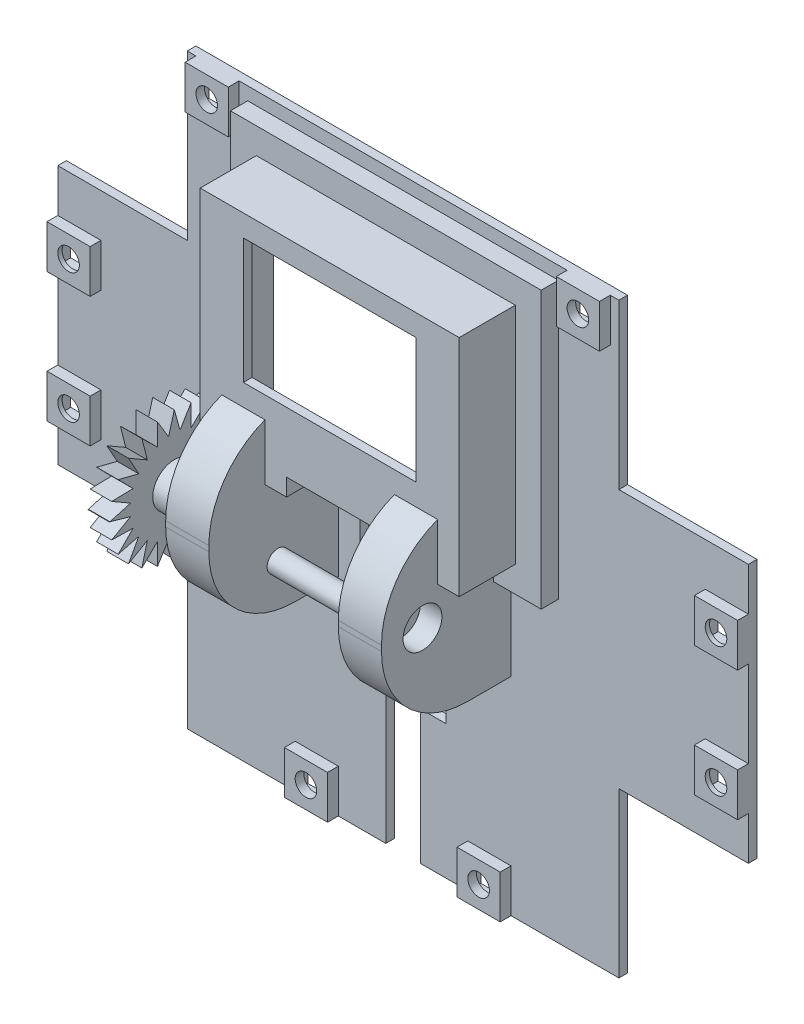
SolidWorks part; units mm, degrees
material "ABS"
ref_plane "Plan de face" through (0, 0, 0) normal (0, 0, 1) x (1, 0, 0)
ref_plane "Plan de dessus" through (0, 0, 0) normal (0, 1, 0) x (1, 0, 0)
ref_plane "Plan de droite" through (0, 0, 0) normal (1, 0, 0) x (0, 0, -1)
sketch "Esquisse1" plane through (0, 0, 0) normal (0, 0, 1) x (1, 0, 0)
  line L0 (0, 0) -> (0, 87) construction
  line L1 (-50, -68) -> (50, -68)
  line L2 (-50, -68) -> (-50, 68)
  line L3 (-50, 68) -> (50, 68)
  line L4 (50, -68) -> (50, 68)
  line L5 (-50, -68) -> (50, 68) construction
  line L6 (-50, 68) -> (50, -68) construction
  line L7 (-34, 3) -> (34, 3)
  line L8 (-34, 3) -> (-34, 63)
  line L9 (-34, 63) -> (34, 63)
  line L10 (34, 3) -> (34, 63)
  line L11 (0, 87) -> (0, -87) construction
  line L13 (-10, 3) -> (10, 3)
  line L14 (-10, 3) -> (-10, -37)
  line L15 (-10, -68) -> (10, -68)
  line L16 (10, 3) -> (10, -37)
  line L17 (-10, 3) -> (10, 3)
  line L18 (-10, 3) -> (-10, -37)
  line L19 (-10, -37) -> (10, -37)
  line L20 (10, 3) -> (10, -37)
  point P0 (0, 0)
  dimension "D1" = 136
  dimension "D2" = 100
  dimension "D3" = 68
  dimension "D4" = 60
  dimension "D5" = 16
  dimension "D6" = 5
  dimension "D7" = 174
  dimension "D8" = 87
  dimension "D9" = 20
  dimension "D10" = 24
  dimension "D11" = 40
extrude "Boss.-Extru.1" add sketch "Esquisse1" along normal blind 2 contours L1 L4 L3 L2 L19 L14 L7 L8 L9 L10 L16 region at (-48.3119, 0, 0)
sketch "Esquisse2" plane through (0, 0, 2) normal (0, 0, 1) x (1, 0, 0)
  line L0 (-34, 63) -> (34, 63) construction
  line L1 (-36, 65) -> (36, 65)
  line L2 (-36, 65) -> (-36, 1)
  line L3 (-36, 1) -> (36, 1)
  line L4 (36, 65) -> (36, 1)
  line L5 (-34, 3) -> (-34, 63) construction
  line L6 (34, 3) -> (34, 63) construction
  line L7 (10, 3) -> (34, 3) construction
  line L9 (-34, 63) -> (34, 63)
  line L10 (-34, 63) -> (-34, 3)
  line L11 (-34, 3) -> (34, 3)
  line L12 (34, 63) -> (34, 3)
  line L13 (-10, 3) -> (10, 3)
  line L14 (-10, 3) -> (-10, 1)
  line L15 (-10, 1) -> (10, 1)
  line L16 (10, 3) -> (10, 1)
  line M6 (-10, -37) -> (-10, 3)
  line M7 (-10, 3) -> (-34, 3)
  line M8 (-34, 3) -> (-34, 63)
  line M9 (-34, 63) -> (34, 63)
  line M10 (34, 63) -> (34, 3)
  line M11 (34, 3) -> (10, 3)
  line M12 (10, 3) -> (10, -37)
  dimension "D1" = 2
  dimension "D2" = 2
  dimension "D3" = 2
  dimension "D4" = 2
  dimension "D5" = 20
extrude "Boss.-Extru.2" add sketch "Esquisse2" along normal blind 4 contours L4 L1 L2 L3 M6 M7 M8 M9 M10 M11 M12 region at (0, 64.0367, 2)
sketch "Esquisse3" plane through (0, 0, 6) normal (0, 0, 1) x (1, 0, 0)
  line L1 (-34, 63) -> (34, 63)
  line L2 (-34, 63) -> (-34, 3)
  line L3 (-34, 3) -> (34, 3)
  line L4 (34, 63) -> (34, 3)
  line L5 (-28, 57) -> (28, 57)
  line L6 (-28, 57) -> (-28, 9)
  line L7 (-28, 9) -> (28, 9)
  line L8 (28, 57) -> (28, 9)
  dimension "D1" = 6
  dimension "D2" = 6
  dimension "D3" = 6
  dimension "D4" = 6
extrude "Boss.-Extru.3" add sketch "Esquisse3" against normal blind 2
sketch "Esquisse4" plane through (0, 0, 6) normal (0, 0, 1) x (1, 0, 0)
  line L1 (-28, 57) -> (28, 57)
  line L2 (-28, 57) -> (-28, 9)
  line L3 (-28, 9) -> (28, 9)
  line L4 (28, 57) -> (28, 9)
  line L5 (-30, 59) -> (30, 59)
  line L6 (-30, 59) -> (-30, 7)
  line L7 (-30, 7) -> (30, 7)
  line L8 (30, 59) -> (30, 7)
  dimension "D1" = 2
  dimension "D2" = 2
  dimension "D3" = 2
  dimension "D4" = 2
extrude "Boss.-Extru.4" add sketch "Esquisse4" along normal blind 13
sketch "Esquisse5" plane through (0, 0, 19) normal (0, 0, 1) x (1, 0, 0)
  line L1 (-28, 57) -> (28, 57)
  line L2 (-28, 57) -> (-28, 9)
  line L3 (-28, 9) -> (28, 9)
  line L4 (28, 57) -> (28, 9)
extrude "Boss.-Extru.5" add sketch "Esquisse5" against normal blind 2
sketch "Esquisse6" plane through (0, 0, 19) normal (0, 0, 1) x (1, 0, 0)
  line L1 (-10, 1) -> (10, 1)
  line L2 (-10, 1) -> (-10, 11)
  line L3 (-10, 11) -> (10, 11)
  line L4 (10, 1) -> (10, 11)
  dimension "D1" = 20
  dimension "D2" = 10
extrude "Enlèv. mat.-Extru.1" cut sketch "Esquisse6" against normal blind 35
sketch "Esquisse9" plane through (0, 0, 2) normal (0, 0, 1) x (1, 0, 0)
  line L0 (0, 0) -> (50, 0) construction
  line L1 (50, -68) -> (50, 68) construction
  line L2 (50, 0) -> (-50, 0) construction
  line L3 (-50, -68) -> (-50, 68) construction
  line L4 (-36, 1) -> (-10, 1) construction
  line L5 (-50, 20) -> (-48, 20)
  line L6 (-50, 20) -> (-50, -20)
  line L7 (-50, -20) -> (-48, -20)
  line L8 (-48, 20) -> (-48, -20)
  line L9 (50, 20) -> (48, 20)
  line L10 (50, 20) -> (50, -20)
  line L11 (50, -20) -> (48, -20)
  line L12 (48, 20) -> (48, -20)
  line L13 (-25, -20) -> (-15, -20)
  line L14 (-25, -20) -> (-25, 1)
  line L15 (-25, 1) -> (-15, 1)
  line L16 (-15, -20) -> (-15, 1)
  line L17 (10, 1) -> (36, 1) construction
  line L18 (15, 1) -> (25, 1)
  line L19 (15, 1) -> (15, -20)
  line L20 (15, -20) -> (25, -20)
  line L21 (25, 1) -> (25, -20)
  line L22 (-10, 1) -> (-10, -37) construction
  line L23 (10, 1) -> (10, -37) construction
  dimension "D1" = 2
  dimension "D2" = 40
  dimension "D3" = 20
  dimension "D4" = 40
  dimension "D5" = 2
  dimension "D6" = 20
  dimension "D7" = 10
  dimension "D8" = 10
  dimension "D9" = 21
  dimension "D10" = 21
  dimension "D11" = 5
  dimension "D12" = 5
extrude "Boss.-Extru.9" add sketch "Esquisse9" along normal blind 30
fillet "Congé5" radius 20 4 edges at (49, -20, 32) (49, 20, 32) (-49, -20, 32) (-49, 20, 32)
sketch "Esquisse10" plane through (0, 0, 6) normal (0, 0, 1) x (1, 0, 0)
  line L0 (-30, 7) -> (-10, 7) construction
  line L1 (-25, 1) -> (-15, 1)
  line L2 (-25, 1) -> (-25, 7)
  line L3 (-25, 7) -> (-15, 7)
  line L4 (-15, 1) -> (-15, 7)
  line L5 (10, 7) -> (30, 7) construction
  line L6 (15, 1) -> (25, 1)
  line L7 (15, 1) -> (15, 7)
  line L8 (15, 7) -> (25, 7)
  line L9 (25, 1) -> (25, 7)
  dimension "D1" = 10
  dimension "D2" = 10
extrude "Boss.-Extru.10" add sketch "Esquisse10" along normal blind 26
sketch "Esquisse11" plane through (0, 0, 19) normal (0, 0, 1) x (1, 0, 0)
  line L1 (-25, 7) -> (-15, 7)
  line L2 (-25, 7) -> (-25, 20)
  line L3 (-25, 20) -> (-15, 20)
  line L4 (-15, 7) -> (-15, 20)
  line L5 (15, 7) -> (25, 7)
  line L6 (15, 7) -> (15, 20)
  line L7 (15, 20) -> (25, 20)
  line L8 (25, 7) -> (25, 20)
  dimension "D1" = 13
  dimension "D2" = 13
  dimension "D3" = 10
  dimension "D4" = 10
extrude "Boss.-Extru.11" add sketch "Esquisse11" along normal blind 13
fillet "Congé6" radius 20 2 edges at (20, 20, 32) (-20, 20, 32)
fillet "Congé7" radius 20 2 edges at (20, -20, 32) (-20, -20, 32)
sketch "Esquisse12" plane through (-15, 0, 0) normal (1, 0, 0) x (0, 0, -1)
  line L0 (0, 0) -> (-32, 0) construction
  line L1 (-16, 0) -> (-16, -19.5959) construction
  line L2 (-16, 0) -> (-16, -9.798) construction
  arc A0 (-32, 0) -> (-12, -20) centre (-12, 0) ccw construction
  circle A1 centre (-16, -9.798) radius 2.5
  dimension "D1" = 5
extrude "Boss.-Extru.12" add sketch "Esquisse12" along normal blind 36
sketch "Esquisse13" plane through (50, 0, 0) normal (1, 0, 0) x (0, 0, -1)
  line L0 (0, 0) -> (-32, 0) construction
  line L1 (-32, 0) -> (-27, 0) construction
  arc A0 (-32, 0) -> (-12, -20) centre (-12, 0) ccw construction
  circle A1 centre (-22.5, 0) radius 4.5
  dimension "D2" = 9
  dimension "D1" = 5
extrude "Enlèv. mat.-Extru.2" cut sketch "Esquisse13" against normal blind 30
sketch "Esquisse14" plane through (-50, 0, 0) normal (-1, 0, 0) x (0, 0, 1)
  line L0 (0, 0) -> (32, 0) construction
  line L1 (32, 0) -> (27, 0) construction
  circle A0 centre (22.5, 0) radius 4.5
  dimension "D2" = 9
  dimension "D1" = 5
extrude "Enlèv. mat.-Extru.4" cut sketch "Esquisse14" against normal blind 17
sketch "Esquisse15" plane through (-25, 0, 0) normal (-1, 0, 0) x (0, 0, 1)
  line L0 (0, 0) -> (32, 0) construction
  line L1 (32, 0) -> (27.5, 0) construction
  circle A0 centre (22.5, 0) radius 5
  dimension "D2" = 10
  dimension "D1" = 4.5
extrude "Boss.-Extru.13" add sketch "Esquisse15" along normal blind 12.5
sketch "Esquisse16" plane through (0, 0, 2) normal (0, 0, 1) x (1, 0, 0)
  line L0 (-47.5, 0) -> (47.5, 0) construction
  line L1 (-47.5, 0) -> (-38, 0) construction
  line L2 (-38, 0) -> (-37.5, 0) construction
  line L4 (-37.5, 0) -> (-36.5, 0)
  line L5 (-37.5, 0) -> (-37.5, 1)
  line L6 (-37.5, 1) -> (-36.5, 1)
  line L7 (-36.5, 0) -> (-36.5, 1)
  line L8 (-37.5, 0) -> (-36.5, 0)
  line L9 (-37.5, 0) -> (-37.5, -1)
  line L10 (-37.5, -1) -> (-36.5, -1)
  line L11 (-36.5, 0) -> (-36.5, -1)
  dimension "D1" = 95
  dimension "D2" = 2.5
  dimension "D3" = 9.5
  dimension "D4" = 0.5
  dimension "D5" = 1
  dimension "D6" = 1
  dimension "D7" = 1
extrude "Boss.-Extru.14" add sketch "Esquisse16" along normal blind 2 contours L4 L7 L6 L5 | L11 L4 L9 L10 region at (-37, 0.5, 2) region at (-37, -0.5, 2)
sketch "Esquisse17" plane through (-37.5, 0, 0) normal (-1, 0, 0) x (0, 0, 1)
  line L0 (22.5, 5) -> (22.5, -5) construction
  line L1 (0, 0) -> (22.5, 0) construction
  circle A0 centre (22.5, 0) radius 5 construction
  circle A1 centre (22.5, 0) radius 5 construction
  circle A2 centre (22.5, 0) radius 15
  dimension "D1" = 30
extrude "Boss.-Extru.16" add sketch "Esquisse17" against normal blind 5
sketch "Esquisse18" plane through (-50, 0, 0) normal (-1, 0, 0) x (0, 0, 1)
  circle A0 centre (22.5, 0) radius 4.5
extrude "Enlèv. mat.-Extru.5" cut sketch "Esquisse18" against normal blind 16
sketch "Esquisse23" plane through (-37.5, 0, 0) normal (-1, 0, 0) x (0, 0, 1)
  line L0 (22.5, 0) -> (22.5, 15) construction
  line L1 (22.5, 15) -> (22.5, -15) construction
  line L2 (22.5, 0) -> (7.5, 0) construction
  line L3 (7.5, 0) -> (37.5, 0) construction
  line L4 (22.5, 15) -> (23.92, 9.8987)
  line L5 (22.5, 15) -> (21.07, 9.8972)
  line L6 (21.3706, 9.936) -> (18.6136, 14.4878)
  line L7 (18.6136, 14.4878) -> (18.6136, 9.2139)
  line L8 (22.5, 0) -> (18.6136, 14.4878) construction
  line L9 (22.5, 0) -> (14.9926, 12.9861) construction
  line L10 (22.5, 0) -> (11.8844, 10.5976) construction
  line L11 (22.5, 0) -> (9.5011, 7.4853) construction
  line L12 (22.5, 0) -> (8.0056, 3.8618) construction
  line L13 (11.8844, 10.5976) -> (16.4547, 7.9658)
  line L14 (14.4531, 5.937) -> (11.8844, 10.5976)
  line L15 (9.5011, 7.4853) -> (13.2133, 3.7091)
  line L16 (9.5011, 7.4853) -> (14.6367, 6.1781)
  line L17 (14.9926, 12.9861) -> (18.7752, 9.2804)
  line L18 (14.9926, 12.9861) -> (16.3085, 7.8527)
  line L19 (13.3259, 3.9795) -> (8.0056, 3.8618)
  line L20 (8.0056, 3.8618) -> (12.5759, 1.23)
  line L21 (7.5, -0.0255) -> (12.6004, 1.4132)
  line L22 (7.5, -0.0255) -> (12.6038, -1.4368)
  line L23 (37.5, -0.0255) -> (32.3996, 1.4132)
  line L24 (35.4989, 7.4853) -> (31.7867, 3.7091)
  line L25 (36.9944, 3.8618) -> (32.4241, 1.23)
  line L26 (31.6741, 3.9795) -> (36.9944, 3.8618)
  line L27 (35.4989, 7.4853) -> (30.3633, 6.1781)
  line L28 (30.5469, 5.937) -> (33.1156, 10.5976)
  line L29 (33.1156, 10.5976) -> (28.5453, 7.9658)
  line L30 (30.0074, 12.9861) -> (28.6915, 7.8527)
  line L31 (30.0074, 12.9861) -> (26.2248, 9.2804)
  line L32 (26.3864, 14.4878) -> (26.3864, 9.2139)
  line L33 (23.6294, 9.936) -> (26.3864, 14.4878)
  line L34 (22.5, 15) -> (23.93, 9.8972)
  line L35 (37.5, 0.0255) -> (32.3996, -1.4132)
  line L36 (36.9944, -3.8618) -> (32.4241, -1.23)
  line L37 (31.6741, -3.9795) -> (36.9944, -3.8618)
  line L38 (35.4989, -7.4853) -> (31.7867, -3.7091)
  line L39 (35.4989, -7.4853) -> (30.3633, -6.1781)
  line L40 (30.5469, -5.937) -> (33.1156, -10.5976)
  line L41 (33.1156, -10.5976) -> (28.5453, -7.9658)
  line L42 (30.0074, -12.9861) -> (28.6915, -7.8527)
  line L43 (30.0074, -12.9861) -> (26.2248, -9.2804)
  line L44 (26.3864, -14.4878) -> (26.3864, -9.2139)
  line L45 (23.6294, -9.936) -> (26.3864, -14.4878)
  line L46 (22.5, -15) -> (23.92, -9.8987)
  line L47 (22.5, -15) -> (21.07, -9.8972)
  line L48 (21.3706, -9.936) -> (18.6136, -14.4878)
  line L49 (18.6136, -14.4878) -> (18.6136, -9.2139)
  line L50 (14.9926, -12.9861) -> (18.7752, -9.2804)
  line L51 (14.9926, -12.9861) -> (16.3085, -7.8527)
  line L52 (11.8844, -10.5976) -> (16.4547, -7.9658)
  line L53 (14.4531, -5.937) -> (11.8844, -10.5976)
  line L54 (9.5011, -7.4853) -> (14.6367, -6.1781)
  line L55 (9.5011, -7.4853) -> (13.2133, -3.7091)
  line L56 (13.3259, -3.9795) -> (8.0056, -3.8618)
  line L57 (8.0056, -3.8618) -> (12.5759, -1.23)
  line L58 (7.5, 0.0255) -> (12.6004, -1.4132)
  circle A0 centre (22.5, 0) radius 15 construction
  circle A1 centre (22.5, 0) radius 15
  circle A2 centre (22.5, 0) radius 10
  circle M34 centre (22.5, 0) radius 15
  dimension "D2" = 20
  dimension "D7" = 3.92
  dimension "D8" = 2.85
  dimension "D9" = 1.42
  dimension "D10" = 2.85
extrude "Enlèv. mat.-Extru.7" cut sketch "Esquisse23" against normal blind 5 contours L18 L13 M34 | L17 L7 M34 | L6 L5 M34 | L34 L33 M34 | L32 L31 M34 | L30 L29 M34 | L24 L26 M34 | L28 L27 M34 | L35 L25 L23 M34 | L36 L23 L35 M34 | L38 L37 M34 | L39 L40 M34 | L42 L41 M34 | L44 L43 M34 | L46 L45 M34 | L47 L48 M34 | L50 L49 M34 | L52 L51 M34 | L54 L53 M34 | L55 L56 M34 | L57 L22 M34 | L58 L21 L20 M34 | L19 L15 M34 | L16 L14 M34 region at (-37.5, 13.3067, 24.2457) region at (-37.5, 13.3067, 20.7543) region at (-37.5, 12.3567, 27.6155) region at (-37.5, 12.3567, 17.3845) region at (-37.5, 10.6014, 30.659) region at (-37.5, 10.6014, 14.341) region at (-37.5, 8.1531, 33.1604) region at (-37.5, 8.1531, 11.8396) region at (-37.5, 5.1275, 34.8988) region at (-37.5, 5.1275, 10.1012) region at (-37.5, 1.7356, 35.7641) region at (-37.5, 1.7356, 9.2359) region at (-37.5, -1.7356, 35.7641) region at (-37.5, -1.7576, 9.2275) region at (-37.5, -5.1275, 10.1012) region at (-37.5, -5.1275, 34.8988) region at (-37.5, -8.1531, 11.8396) region at (-37.5, -8.1531, 33.1604) region at (-37.5, -10.6014, 14.341) region at (-37.5, -10.6014, 30.659) region at (-37.5, -12.3567, 17.3845) region at (-37.5, -12.3567, 27.6155) region at (-37.5, -13.3067, 20.7543) region at (-37.5, -13.3034, 24.2437)
sketch "Esquisse24" plane through (0, 0, 19) normal (0, 0, 1) x (1, 0, 0)
  line L0 (30, 59) -> (-30, 59) construction
  line L1 (-20, 54) -> (20, 54)
  line L2 (-20, 54) -> (-20, 25)
  line L3 (-20, 25) -> (20, 25)
  line L4 (20, 54) -> (20, 25)
  line L5 (-30, 59) -> (-30, 7) construction
  line L6 (30, 7) -> (30, 59) construction
  line L7 (-15, 20) -> (-25, 20) construction
  dimension "D1" = 5
  dimension "D2" = 10
  dimension "D3" = 10
  dimension "D4" = 5
extrude "Enlèv. mat.-Extru.8" cut sketch "Esquisse24" against normal blind 10
sketch "Esquisse25" plane through (0, 0, 2) normal (0, 0, 1) x (1, 0, 0)
  line L10 (-50, 63) -> (-36, 63) construction
  line L11 (-43, 58) -> (-43, 68) construction
  line L12 (36, 63) -> (50, 63) construction
  line L13 (43, 58) -> (43, 68) construction
  circle A0 centre (-43, 63) radius 2.5
  circle A1 centre (43, 63) radius 2.5
  dimension "D3" = 5
  dimension "D4" = 5
extrude "Enlèv. mat.-Extru.9" cut sketch "Esquisse25" against normal blind 10
sketch "Esquisse26" plane through (0, 0, 2) normal (0, 0, 1) x (1, 0, 0)
  line L0 (0, 0) -> (0, -68) construction
  line L1 (-50, -68) -> (50, -68) construction
  line L2 (-10, -37) -> (10, -37) construction
  line L3 (-4, -37) -> (4, -37)
  line L4 (-4, -37) -> (-4, -68)
  line L5 (-4, -68) -> (4, -68)
  line L6 (4, -37) -> (4, -68)
  dimension "D1" = 8
  dimension "D2" = 4
extrude "Enlèv. mat.-Extru.10" cut sketch "Esquisse26" against normal blind 10
sketch "Esquisse27" plane through (0, 0, 0) normal (0, 0, -1) x (-1, 0, 0)
  line L0 (-50, -68) -> (50, -68) construction
  line L1 (0, 0) -> (0, -68) construction
  line L2 (-25, -68) -> (-25, -58) construction
  line L3 (-25, -58) -> (25, -58) construction
  line L4 (25, -58) -> (25, -68) construction
  line L5 (-15, -58) -> (-15, -68) construction
  line L6 (-24, -59) -> (-16, -59)
  line L7 (-24, -59) -> (-24, -67)
  line L8 (-24, -67) -> (-16, -67)
  line L9 (-16, -59) -> (-16, -67)
  line L10 (24, -67) -> (16, -67)
  line L11 (16, -59) -> (16, -67)
  line L12 (24, -59) -> (16, -59)
  line L13 (24, -59) -> (24, -67)
  dimension "D1" = 10
  dimension "D2" = 50
  dimension "D3" = 25
  dimension "D4" = 8
  dimension "D5" = 8
  dimension "D6" = 1
  dimension "D7" = 1
  dimension "D8" = 1
extrude "Enlèv. mat.-Extru.11" cut sketch "Esquisse27" against normal blind 2.5
sketch "Esquisse28" plane through (0, 0, 2) normal (0, 0, 1) x (1, 0, 0)
  line L0 (-50, -68) -> (-4, -68) construction
  line L1 (-25, -58) -> (-15, -58)
  line L2 (-25, -58) -> (-25, -68)
  line L3 (-25, -68) -> (-15, -68)
  line L4 (-15, -58) -> (-15, -68)
  line L5 (0, 0) -> (0, -68) construction
  line L6 (-24, -59) -> (-16, -59)
  line L7 (-24, -59) -> (-24, -67)
  line L8 (-24, -67) -> (-16, -67)
  line L9 (-16, -59) -> (-16, -67)
  line L10 (-50, -68) -> (50, -68) construction
  line L11 (25, -68) -> (15, -68)
  line L12 (15, -58) -> (15, -68)
  line L13 (25, -58) -> (15, -58)
  line L14 (25, -58) -> (25, -68)
  line L15 (24, -67) -> (16, -67)
  line L16 (16, -59) -> (16, -67)
  line L17 (24, -59) -> (16, -59)
  line L18 (24, -59) -> (24, -67)
  dimension "D1" = 1
  dimension "D2" = 1
  dimension "D3" = 1
extrude "Boss.-Extru.17" add sketch "Esquisse28" along normal blind 2.5
sketch "Esquisse29" plane through (0, 0, 4.5) normal (0, 0, 1) x (1, 0, 0)
  line L0 (0, 0) -> (0, -67) construction
  line L1 (-24, -59) -> (-16, -59)
  line L2 (-24, -59) -> (-24, -67)
  line L3 (-24, -67) -> (-16, -67)
  line L4 (-16, -59) -> (-16, -67)
  line L5 (24, -67) -> (16, -67)
  line L6 (16, -59) -> (16, -67)
  line L7 (24, -59) -> (16, -59)
  line L8 (24, -59) -> (24, -67)
extrude "Boss.-Extru.18" add sketch "Esquisse29" against normal blind 2
sketch "Esquisse30" plane through (0, 0, 4.5) normal (0, 0, 1) x (1, 0, 0)
  line L0 (-25, -63) -> (-15, -63) construction
  line L1 (-25, -58) -> (-25, -68) construction
  line L2 (-15, -68) -> (-15, -58) construction
  line L3 (-20, -58) -> (-20, -68) construction
  line L4 (-15, -58) -> (-25, -58) construction
  line L5 (-25, -68) -> (-15, -68) construction
  line L6 (0, 0) -> (0, -70.7029) construction
  circle A0 centre (-20, -63) radius 2.5
  circle A1 centre (20, -63) radius 2.5
  dimension "D1" = 5
extrude "Enlèv. mat.-Extru.12" cut sketch "Esquisse30" against normal blind 2 contours A0 | A1
sketch "Esquisse31" plane through (0, 0, 0) normal (0, 0, -1) x (-1, 0, 0)
  line L0 (0, 0) -> (0, 68) construction
  line L1 (-47, 59) -> (-39, 59)
  line L2 (-47, 59) -> (-47, 67)
  line L3 (-47, 67) -> (-39, 67)
  line L4 (-39, 59) -> (-39, 67)
  line L5 (-47, 59) -> (-39, 67) construction
  line L6 (-47, 67) -> (-39, 59) construction
  line L7 (50, 68) -> (-50, 68) construction
  line L8 (47, 67) -> (39, 67)
  line L9 (39, 59) -> (39, 67)
  line L10 (47, 59) -> (39, 59)
  line L11 (47, 59) -> (47, 67)
  point P0 (-43, 63)
  dimension "D1" = 8
  dimension "D2" = 8
extrude "Enlèv. mat.-Extru.13" cut sketch "Esquisse31" against normal blind 2.5
sketch "Esquisse32" plane through (0, 0, 2) normal (0, 0, 1) x (1, 0, 0)
  line L0 (0, 0) -> (0, 68) construction
  line L1 (-50, 68) -> (50, 68) construction
  line L2 (48, 68) -> (38, 68)
  line L3 (-47, 59) -> (-39, 59)
  line L4 (-47, 59) -> (-47, 67)
  line L5 (-47, 67) -> (-39, 67)
  line L6 (-39, 59) -> (-39, 67)
  line L7 (-48, 58) -> (-38, 58)
  line L8 (-48, 58) -> (-48, 68)
  line L9 (-48, 68) -> (-38, 68)
  line L10 (-38, 58) -> (-38, 68)
  line L11 (38, 58) -> (38, 68)
  line L12 (48, 58) -> (38, 58)
  line L13 (48, 58) -> (48, 68)
  line L14 (47, 67) -> (39, 67)
  line L15 (39, 59) -> (39, 67)
  line L16 (47, 59) -> (39, 59)
  line L17 (47, 59) -> (47, 67)
  dimension "D1" = 1
  dimension "D2" = 1
  dimension "D3" = 1
extrude "Boss.-Extru.19" add sketch "Esquisse32" along normal blind 2.5
sketch "Esquisse33" plane through (0, 0, 4.5) normal (0, 0, 1) x (1, 0, 0)
  line L0 (0, 0) -> (0, 68) construction
  line L1 (-47, 67) -> (-39, 67)
  line L2 (-47, 67) -> (-47, 59)
  line L3 (-47, 59) -> (-39, 59)
  line L4 (-39, 67) -> (-39, 59)
  line L5 (-38, 68) -> (38, 68) construction
  line L6 (47, 67) -> (47, 59)
  line L7 (47, 59) -> (39, 59)
  line L8 (39, 67) -> (39, 59)
  line L9 (47, 67) -> (39, 67)
extrude "Boss.-Extru.20" add sketch "Esquisse33" against normal blind 2
sketch "Esquisse34" plane through (0, 0, 4.5) normal (0, 0, 1) x (1, 0, 0)
  line L0 (-38, 68) -> (-48, 68) construction
  line L1 (-48, 68) -> (-48, 58) construction
  line L2 (48, 58) -> (48, 68) construction
  line L3 (48, 68) -> (38, 68) construction
  circle A0 centre (-43, 63) radius 2.5
  circle A1 centre (43, 63) radius 2.5
  dimension "D1" = 5
  dimension "D4" = 5
  dimension "D2" = 5
  dimension "D3" = 5
  dimension "D5" = 5
  dimension "D6" = 5
extrude "Enlèv. mat.-Extru.14" cut sketch "Esquisse34" against normal blind 2
sketch "Esquisse35" plane through (-50, 0, 0) normal (-1, 0, 0) x (0, 0, 1)
  line L0 (0, -68) -> (0, 68) construction
  line L1 (0, 30) -> (2, 30)
  line L2 (0, 30) -> (0, -30)
  line L3 (0, -30) -> (2, -30)
  line L4 (2, 30) -> (2, -30)
  line L5 (2, -68) -> (2, -20) construction
  dimension "D1" = 60
  dimension "D2" = 30
extrude "Boss.-Extru.21" add sketch "Esquisse35" along normal blind 30
sketch "Esquisse36" plane through (50, 0, 0) normal (1, 0, 0) x (0, 0, -1)
  line L0 (-2, 20) -> (-2, 68) construction
  line L1 (-2, 30) -> (0, 30)
  line L2 (-2, 30) -> (-2, -30)
  line L3 (-2, -30) -> (0, -30)
  line L4 (0, 30) -> (0, -30)
  line L5 (0, -68) -> (0, 68) construction
  line L6 (-12, -20) -> (-2, -20) construction
  dimension "D1" = 60
  dimension "D2" = 10
extrude "Boss.-Extru.22" add sketch "Esquisse36" along normal blind 30
sketch "Esquisse37" plane through (0, 0, 2) normal (0, 0, 1) x (1, 0, 0)
  line L0 (-80, 0) -> (-48, 0) construction
  line L1 (-79, 19) -> (-71, 19)
  line L2 (-79, 19) -> (-79, 11)
  line L3 (-79, 11) -> (-71, 11)
  line L4 (-71, 19) -> (-71, 11)
  line L5 (-80, -30) -> (-80, 30) construction
  line L6 (-48, -20) -> (-48, 20) construction
  line L7 (-80, 30) -> (-50, 30) construction
  line L8 (-79, -11) -> (-71, -11)
  line L9 (-71, -19) -> (-71, -11)
  line L10 (-79, -19) -> (-71, -19)
  line L11 (-79, -19) -> (-79, -11)
  dimension "D1" = 8
  dimension "D2" = 8
  dimension "D3" = 1
  dimension "D4" = 11
extrude "Enlèv. mat.-Extru.15" cut sketch "Esquisse37" against normal blind 30
sketch "Esquisse38" plane through (0, 0, 2) normal (0, 0, 1) x (1, 0, 0)
  line L0 (-80, -30) -> (-80, 30) construction
  line L1 (-80, 20) -> (-70, 20)
  line L2 (-80, 20) -> (-80, 10)
  line L3 (-80, 10) -> (-70, 10)
  line L4 (-70, 20) -> (-70, 10)
  line L5 (-80, 0) -> (-48, 0) construction
  line L6 (-48, -20) -> (-48, 20) construction
  line L7 (-79, 11) -> (-71, 11) construction
  line L8 (-80, -10) -> (-70, -10)
  line L9 (-79, 19) -> (-71, 19)
  line L10 (-79, 19) -> (-79, 11)
  line L11 (-79, 11) -> (-71, 11)
  line L12 (-71, 19) -> (-71, 11)
  line L13 (-70, -20) -> (-70, -10)
  line L14 (-80, -20) -> (-70, -20)
  line L15 (-80, -20) -> (-80, -10)
  line L16 (-79, -11) -> (-71, -11)
  line L17 (-71, -19) -> (-71, -11)
  line L18 (-79, -19) -> (-71, -19)
  line L19 (-79, -19) -> (-79, -11)
  dimension "D1" = 10
  dimension "D2" = 1
  dimension "D3" = 10
extrude "Boss.-Extru.23" add sketch "Esquisse38" along normal blind 2.5
sketch "Esquisse39" plane through (-71, 0, 0) normal (-1, 0, 0) x (0, 0, 1)
  line L0 (0, 11) -> (4.5, 11) construction
  line L1 (4.5, 19) -> (3.5, 19)
  line L2 (4.5, 19) -> (4.5, 11)
  line L3 (4.5, 11) -> (3.5, 11)
  line L4 (3.5, 19) -> (3.5, 11)
  dimension "D1" = 1
extrude "Boss.-Extru.24" add sketch "Esquisse39" along normal blind 8
sketch "Esquisse40" plane through (-71, 0, 0) normal (-1, 0, 0) x (0, 0, 1)
  line L0 (0, -19) -> (4.5, -19) construction
  line L1 (4.5, -11) -> (3.5, -11)
  line L2 (4.5, -11) -> (4.5, -19)
  line L3 (4.5, -19) -> (3.5, -19)
  line L4 (3.5, -11) -> (3.5, -19)
  dimension "D1" = 1
extrude "Boss.-Extru.25" add sketch "Esquisse40" along normal blind 8
sketch "Esquisse41" plane through (0, 0, 4.5) normal (0, 0, 1) x (1, 0, 0)
  line L0 (-70, 20) -> (-80, 20) construction
  line L1 (-70, 10) -> (-70, 20) construction
  line L2 (-70, -10) -> (-80, -10) construction
  line L3 (-70, -20) -> (-70, -10) construction
  circle A0 centre (-75, 15) radius 2.5
  circle A1 centre (-75, -15) radius 2.5
  dimension "D1" = 5
  dimension "D2" = 5
  dimension "D3" = 5
  dimension "D4" = 5
  dimension "D5" = 5
  dimension "D6" = 5
extrude "Enlèv. mat.-Extru.16" cut sketch "Esquisse41" against normal blind 8
sketch "Esquisse42" plane through (0, 0, 2) normal (0, 0, 1) x (1, 0, 0)
  line L0 (80, 30) -> (50, 30) construction
  line L1 (79, 19) -> (71, 19)
  line L2 (79, 19) -> (79, 11)
  line L3 (79, 11) -> (71, 11)
  line L4 (71, 19) -> (71, 11)
  line L5 (80, 30) -> (80, -30) construction
  line L6 (48, 0) -> (80, 0) construction
  line L7 (48, 20) -> (48, -20) construction
  line L8 (79, -11) -> (71, -11)
  line L9 (71, -19) -> (71, -11)
  line L10 (79, -19) -> (71, -19)
  line L11 (79, -19) -> (79, -11)
  dimension "D1" = 11
  dimension "D2" = 8
  dimension "D3" = 8
  dimension "D4" = 1
extrude "Enlèv. mat.-Extru.17" cut sketch "Esquisse42" against normal blind 8
sketch "Esquisse43" plane through (0, 0, 2) normal (0, 0, 1) x (1, 0, 0)
  line L0 (80, 30) -> (80, -30) construction
  line L1 (80, 20) -> (70, 20)
  line L2 (80, 20) -> (80, 10)
  line L3 (80, 10) -> (70, 10)
  line L4 (70, 20) -> (70, 10)
  line L5 (48, 0) -> (80, 0) construction
  line L6 (48, 20) -> (48, -20) construction
  line L7 (71, 11) -> (79, 11) construction
  line L9 (80, -20) -> (80, -10)
  line L10 (71, 19) -> (79, 19)
  line L11 (71, 19) -> (71, 11)
  line L12 (71, 11) -> (79, 11)
  line L13 (79, 19) -> (79, 11)
  line L14 (80, -20) -> (70, -20)
  line L15 (70, -20) -> (70, -10)
  line L16 (80, -10) -> (70, -10)
  line L17 (71, -11) -> (79, -11)
  line L18 (79, -19) -> (79, -11)
  line L19 (71, -19) -> (79, -19)
  line L20 (71, -19) -> (71, -11)
  dimension "D1" = 1
  dimension "D2" = 10
  dimension "D3" = 10
extrude "Boss.-Extru.26" add sketch "Esquisse43" along normal blind 2.5
sketch "Esquisse44" plane through (71, 0, 0) normal (1, 0, 0) x (0, 0, -1)
  line L0 (0, 11) -> (-4.5, 11) construction
  line L1 (-4.5, 19) -> (-3.5, 19)
  line L2 (-4.5, 19) -> (-4.5, 11)
  line L3 (-4.5, 11) -> (-3.5, 11)
  line L4 (-3.5, 19) -> (-3.5, 11)
  dimension "D1" = 1
extrude "Boss.-Extru.27" add sketch "Esquisse44" along normal blind 8
sketch "Esquisse45" plane through (71, 0, 0) normal (1, 0, 0) x (0, 0, -1)
  line L0 (0, -11) -> (-4.5, -11) construction
  line L1 (-4.5, -19) -> (-3.5, -19)
  line L2 (-4.5, -19) -> (-4.5, -11)
  line L3 (-4.5, -11) -> (-3.5, -11)
  line L4 (-3.5, -19) -> (-3.5, -11)
  dimension "D1" = 1
extrude "Boss.-Extru.28" add sketch "Esquisse45" along normal blind 8
sketch "Esquisse46" plane through (0, 0, 4.5) normal (0, 0, 1) x (1, 0, 0)
  line L0 (80, -10) -> (70, -10) construction
  line L1 (70, -10) -> (70, -20) construction
  line L2 (48, 0) -> (80, 0) construction
  line L3 (48, 20) -> (48, -20) construction
  line L4 (80, 10) -> (80, -10) construction
  circle A1 centre (75, -15) radius 2.5
  circle A2 centre (75, 15) radius 2.5
  dimension "D2" = 5
  dimension "D1" = 5
  dimension "D3" = 5
extrude "Enlèv. mat.-Extru.18" cut sketch "Esquisse46" against normal blind 8
sketch "Esquisse47" plane through (0, 0, 2) normal (0, 0, 1) x (1, 0, 0)
  line L1 (-50, 20) -> (-48, 20)
  line L2 (-50, 20) -> (-50, -20)
  line L3 (-50, -20) -> (-48, -20)
  line L4 (-48, 20) -> (-48, -20)
  line L5 (48, 20) -> (50, 20)
  line L6 (48, 20) -> (48, -20)
  line L7 (48, -20) -> (50, -20)
  line L8 (50, 20) -> (50, -20)
extrude "Enlèv. mat.-Extru.19" cut sketch "Esquisse47" along normal blind 30
